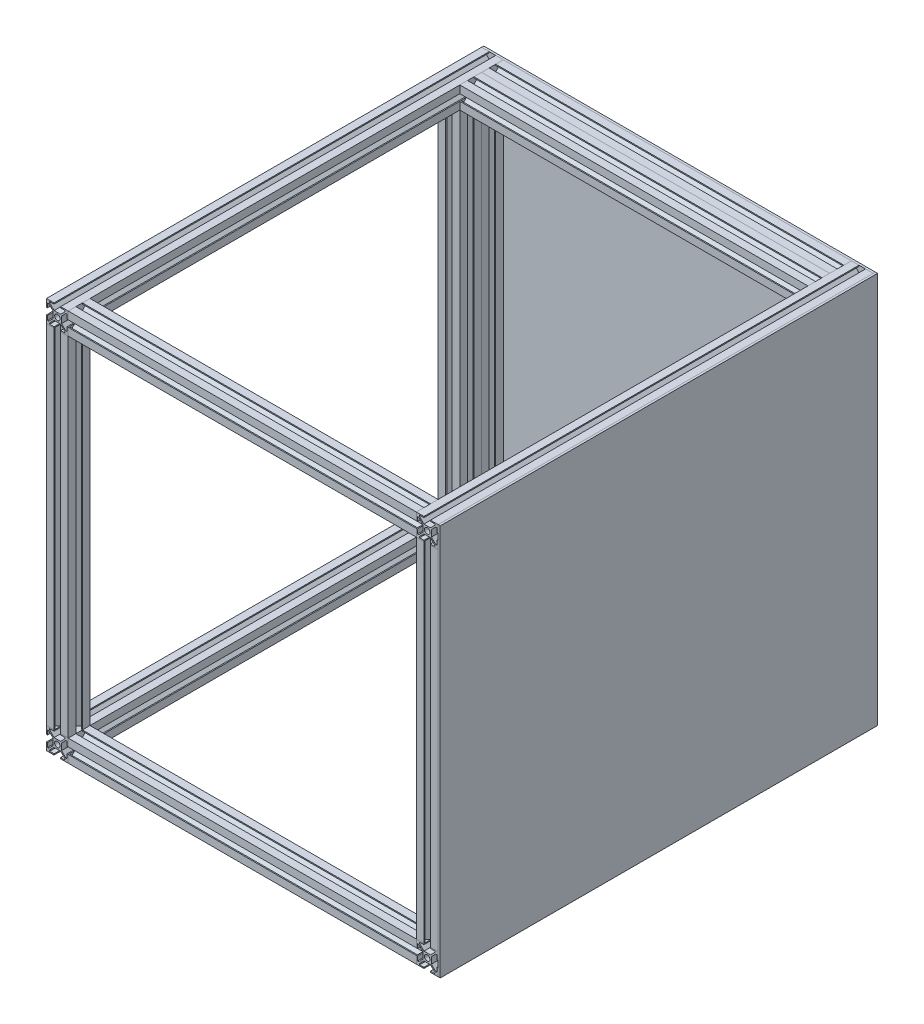
SolidWorks part; units mm, degrees
material "6063-T1"
ref_plane "Front Plane" through (0, 0, 0) normal (1, 0, 0) x (0, 1, 0)
ref_plane "Top Plane" through (0, 0, 0) normal (0, 0, 1) x (0, 1, 0)
ref_plane "Right Plane" through (0, 0, 0) normal (0, 1, 0) x (-1, 0, 0)
ref_axis "Axis1" through (0, 0, 0) along (0, 0, 1)
sketch "Sketch2" plane through (0, 0, 0) normal (1, 0, 0) x (0, 1, 0)
  line L5 (-180, 3) -> (-180, 10)
  line L67 (-180, 10) -> (-160, 10) construction
  line L68 (-180, 10) -> (-180, -10) construction
  line L69 (-180, -10) -> (-160, -10) construction
  line L70 (-160, 10) -> (-160, -10) construction
  line L72 (-160, 0) -> (160, 0) construction
  line L73 (-180, 10) -> (-173, 10)
  line L74 (-173, 10) -> (-173, 9)
  line L75 (-173, 9) -> (-177, 9)
  line L76 (-177, 9) -> (-177, 7.9857)
  line L77 (-177, 7.9857) -> (-173, 3.9857)
  line L78 (-173, 3.9857) -> (-170, 3.9857)
  line L79 (-180, 3) -> (-179, 3)
  line L80 (-179, 3) -> (-179, 7)
  line L81 (-179, 7) -> (-177.9857, 7)
  line L82 (-177.9857, 7) -> (-173.9857, 3)
  line L83 (-173.9857, 3) -> (-173.9857, 0)
  line L84 (-173.9857, 3) -> (-173, 3.9857) construction
  line L85 (-167, 10) -> (-160, 10)
  line L86 (-160, 10) -> (-160, 3)
  line L87 (-160, 3) -> (-161, 3)
  line L88 (-161, 3) -> (-161, 7)
  line L89 (-161, 7) -> (-162.0143, 7)
  line L90 (-162.0143, 7) -> (-166.0143, 3)
  line L91 (-166.0143, 3) -> (-166.0143, 0)
  line L92 (-167, 10) -> (-167, 9)
  line L93 (-167, 9) -> (-163, 9)
  line L94 (-163, 9) -> (-163, 7.9857)
  line L95 (-163, 7.9857) -> (-167, 3.9857)
  line L96 (-167, 3.9857) -> (-170, 3.9857)
  line L97 (-167, 3.9857) -> (-166.0143, 3) construction
  line L98 (-160, -3) -> (-160, -10)
  line L99 (-160, -10) -> (-167, -10)
  line L100 (-167, -10) -> (-167, -9)
  line L101 (-167, -9) -> (-163, -9)
  line L102 (-163, -9) -> (-163, -7.9857)
  line L103 (-163, -7.9857) -> (-167, -3.9857)
  line L104 (-167, -3.9857) -> (-170, -3.9857)
  line L105 (-160, -3) -> (-161, -3)
  line L106 (-161, -3) -> (-161, -7)
  line L107 (-161, -7) -> (-162.0143, -7)
  line L108 (-162.0143, -7) -> (-166.0143, -3)
  line L109 (-166.0143, -3) -> (-166.0143, 0)
  line L110 (-166.0143, -3) -> (-167, -3.9857) construction
  line L111 (-173, -10) -> (-180, -10)
  line L112 (-180, -10) -> (-180, -3)
  line L113 (-180, -3) -> (-179, -3)
  line L114 (-179, -3) -> (-179, -7)
  line L115 (-179, -7) -> (-177.9857, -7)
  line L116 (-177.9857, -7) -> (-173.9857, -3)
  line L117 (-173.9857, -3) -> (-173.9857, 0)
  line L118 (-173, -10) -> (-173, -9)
  line L119 (-173, -9) -> (-177, -9)
  line L120 (-177, -9) -> (-177, -7.9857)
  line L121 (-177, -7.9857) -> (-173, -3.9857)
  line L122 (-173, -3.9857) -> (-170, -3.9857)
  line L123 (-173, -3.9857) -> (-173.9857, -3) construction
  circle A0 centre (-170, 0) radius 2.5
  point P0 (-192.5803, 22.4509)
  point P72 (-160, 0)
  point P107 (-170, 0)
  dimension "D5" = 5
  dimension "D1" = 20
  dimension "D2" = 45
  dimension "D4" = 6
  dimension "D3" = 14
  dimension "D8" = 45
  dimension "D7" = 1
  dimension "D6" = 4
sketch "Sketch1" plane through (0, 0, 0) normal (0, 0, 1) x (0, 1, 0)
  line L0 (-160, 160) -> (160, -160) construction
  line L5 (-160, 160) -> (160, 160)
  line L6 (-160, 160) -> (-160, -160)
  line L7 (-160, -160) -> (160, -160)
  line L8 (160, 160) -> (160, -160)
  point P108 (0, 0)
  dimension "D1" = 320
  dimension "D2" = 320
sweep "Aluminium Extrsion Base" add profiles "Sketch2" path "Sketch1"
pattern_circular "CirPattern1" count 4 over 360 about axis through (0, 0, 0) along (0, 0, 1) of "Aluminium Extrsion Base"
mirror "Mirror5" about plane through (-160, 167, 10) normal (0, 0, -1) of bodies 122 118 124 123
sketch "Sketch4" plane through (0, 0, -10) normal (0, 0, 1) x (0, 1, 0)
  line L5 (-180, -167) -> (-180, -160)
  line L67 (-180, -160) -> (-160, -160) construction
  line L68 (-180, -160) -> (-180, -180) construction
  line L69 (-180, -180) -> (-160, -180) construction
  line L70 (-160, -160) -> (-160, -180) construction
  line L71 (-160, -167) -> (-160, -170) construction
  line L73 (-180, -160) -> (-173, -160)
  line L74 (-173, -160) -> (-173, -161)
  line L75 (-173, -161) -> (-177, -161)
  line L76 (-177, -161) -> (-177, -162.0896)
  line L77 (-177, -162.0896) -> (-173, -166.0896)
  line L78 (-173, -166.0896) -> (-170, -166.0896)
  line L79 (-180, -167) -> (-179, -167)
  line L80 (-179, -167) -> (-179, -163)
  line L81 (-179, -163) -> (-177.9104, -163)
  line L82 (-177.9104, -163) -> (-173.9104, -167)
  line L83 (-173.9104, -167) -> (-173.9104, -170)
  line L84 (-173.9104, -167) -> (-173, -166.0896) construction
  line L85 (-167, -160) -> (-160, -160)
  line L86 (-160, -160) -> (-160, -167)
  line L87 (-160, -167) -> (-161, -167)
  line L88 (-161, -167) -> (-161, -163)
  line L89 (-161, -163) -> (-162.0896, -163)
  line L90 (-162.0896, -163) -> (-166.0896, -167)
  line L91 (-166.0896, -167) -> (-166.0896, -170)
  line L92 (-167, -160) -> (-167, -161)
  line L93 (-167, -161) -> (-163, -161)
  line L94 (-163, -161) -> (-163, -162.0896)
  line L95 (-163, -162.0896) -> (-167, -166.0896)
  line L96 (-167, -166.0896) -> (-170, -166.0896)
  line L97 (-167, -166.0896) -> (-166.0896, -167) construction
  line L98 (-160, -173) -> (-160, -180)
  line L99 (-160, -180) -> (-167, -180)
  line L100 (-167, -180) -> (-167, -179)
  line L101 (-167, -179) -> (-163, -179)
  line L102 (-163, -179) -> (-163, -177.9104)
  line L103 (-163, -177.9104) -> (-167, -173.9104)
  line L104 (-167, -173.9104) -> (-170, -173.9104)
  line L105 (-160, -173) -> (-161, -173)
  line L106 (-161, -173) -> (-161, -177)
  line L107 (-161, -177) -> (-162.0896, -177)
  line L108 (-162.0896, -177) -> (-166.0896, -173)
  line L109 (-166.0896, -173) -> (-166.0896, -170)
  line L110 (-166.0896, -173) -> (-167, -173.9104) construction
  line L111 (-173, -180) -> (-180, -180)
  line L112 (-180, -180) -> (-180, -173)
  line L113 (-180, -173) -> (-179, -173)
  line L114 (-179, -173) -> (-179, -177)
  line L115 (-179, -177) -> (-177.9104, -177)
  line L116 (-177.9104, -177) -> (-173.9104, -173)
  line L117 (-173.9104, -173) -> (-173.9104, -170)
  line L118 (-173, -180) -> (-173, -179)
  line L119 (-173, -179) -> (-177, -179)
  line L120 (-177, -179) -> (-177, -177.9104)
  line L121 (-177, -177.9104) -> (-173, -173.9104)
  line L122 (-173, -173.9104) -> (-170, -173.9104)
  line L123 (-173, -173.9104) -> (-173.9104, -173) construction
  line L124 (-167, -160) -> (-170, -160) construction
  circle A0 centre (-170, -170) radius 2.5
  point P0 (-192.5803, 22.4509)
  point P72 (-160, -170)
  point P107 (-170, -170)
  dimension "D2" = 45
  dimension "D5" = 5
  dimension "D1" = 20
  dimension "D3" = 14
  dimension "D4" = 6
  dimension "D7" = 1
  dimension "D8" = 45
  dimension "D6" = 4
extrude "Aluminium Extrusion Pillar" add sketch "Sketch4" along normal blind 400 separate body
pattern_circular "CirPattern2" count 4 over 360 about axis through (0, 0, 0) along (0, 0, 1) of bodies 125
ref_plane "Plane2" through (0, 0, 190) normal (0, 0, 1) x (1, 0, 0)
mirror "Mirror4" about plane through (0, 0, 190) normal (0, 0, 1) of bodies 124 118 122 123
sketch "Sketch5" plane through (0, 0, -10) normal (0, 0, -1) x (1, 0, 0)
  line L1 (-180, 180) -> (180, 180)
  line L2 (-180, 180) -> (-180, -180)
  line L3 (-180, -180) -> (180, -180)
  line L4 (180, 180) -> (180, -180)
  line L5 (0, -180) -> (0, 180) construction
  line L6 (-180, 0) -> (180, 0) construction
  circle A0 centre (-170, -170) radius 2.5 construction
  circle A1 centre (170, -170) radius 2.5 construction
  circle A2 centre (170, 170) radius 2.5 construction
  circle A3 centre (-170, 170) radius 2.5 construction
  circle A4 centre (-170, -170) radius 2.5
  circle A5 centre (170, -170) radius 2.5
  circle A6 centre (170, 170) radius 2.5
  circle A7 centre (-170, 170) radius 2.5
  point P308 (0, 0)
extrude "Bottom Plate" add sketch "Sketch5" along normal blind 2 separate body
sketch "Sketch6" plane through (180, 0, 0) normal (1, 0, 0) x (0, 1, 0)
  line L1 (-180, 390) -> (180, 390)
  line L2 (-180, 390) -> (-180, -12)
  line L3 (-180, -12) -> (180, -12)
  line L4 (180, 390) -> (180, -12)
  line L5 (0, -12) -> (0, 390) construction
  line L6 (-180, 189) -> (180, 189) construction
  point P96 (0, 189)
extrude "Back Plate" add sketch "Sketch6" along normal blind 2 separate body
equation "\"extrusion_width\"= 20mm"
equation "\"frame_height\"= 360mm"
equation "\"frame_width\"= 320mm"
equation "\"frame_length\"= 320mm"
equation "\"bed_radius\"= 100mm"
equation "\"bottom_plate_thickness\"=2"
equation "\"D2@Sketch1\"=\"frame_length\""
equation "\"D1@Sketch1\"=\"frame_width\""
equation "\"D1@Sketch2\"=\"extrusion_width\""
equation "\"D1@Aluminium Extrusion Pillar\" = \"frame_height\" + \"extrusion_width\" * 2"
equation "\"D1@Bottom Plate\" = \"bottom_plate_thickness\""
